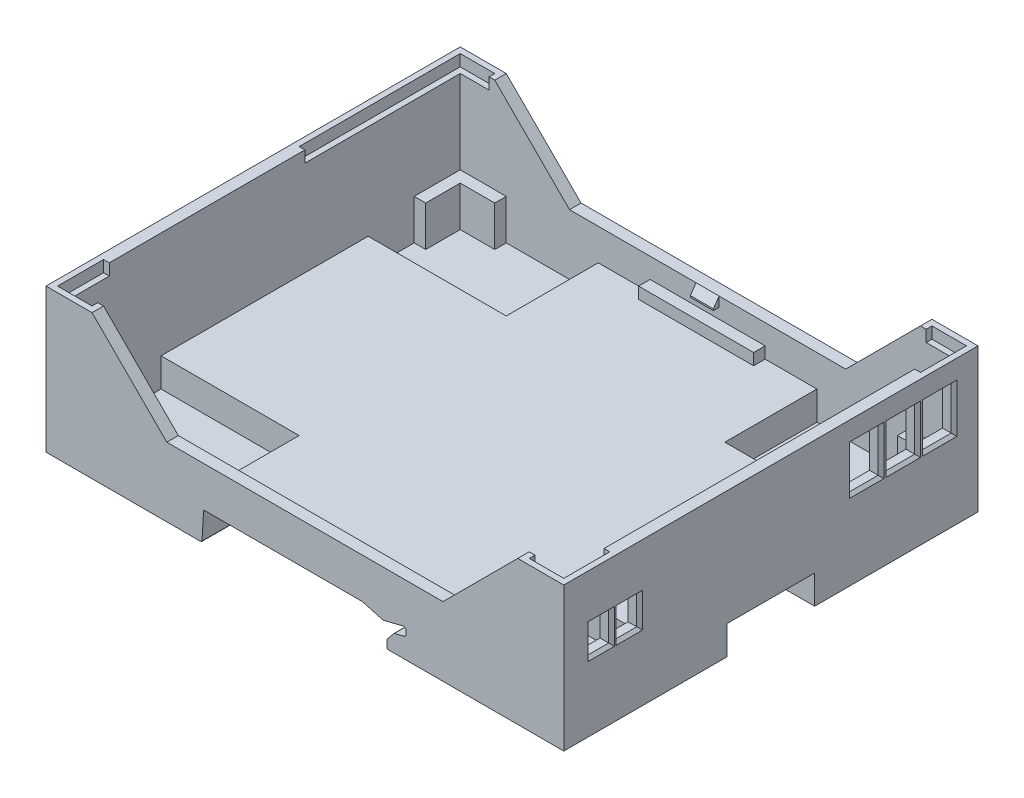
SolidWorks part; units mm, degrees
ref_plane "前视基准面" through (0, 0, 0) normal (0, 0, 1) x (1, 0, 0)
ref_plane "上视基准面" through (0, 0, 0) normal (0, 1, 0) x (1, 0, 0)
ref_plane "右视基准面" through (0, 0, 0) normal (1, 0, 0) x (0, 0, -1)
other "Configuration Table"
sketch "草图1" plane through (0, 0, 0) normal (0, 1, 0) x (1, 0, 0)
  line L1 (-45, -36) -> (45, -36)
  line L2 (-45, -36) -> (-45, 36)
  line L3 (-45, 36) -> (45, 36)
  line L4 (45, -36) -> (45, 36)
  dimension "D1" = 72
  dimension "D2" = 90
  dimension "D3" = 45
  dimension "D4" = 36
extrude "凸台-拉伸1" add sketch "草图1" along normal blind 25
sketch "草图4" plane through (0, 0, 36) normal (0, 0, 1) x (1, 0, 0)
  line L0 (14.3, 0) -> (14.3, 1.5)
  line L1 (-45, 0) -> (45, 0) construction
  line L2 (15.49, 2.9653) -> (17.6, 3.5)
  line L3 (17.6, 3.5) -> (17.6, 5)
  line L4 (17.6, 5) -> (13.5989, 4.0036)
  line L5 (13.5989, 4.0036) -> (10, 5)
  line L6 (10, 5) -> (-17.6, 5)
  line L7 (-17.6, 5) -> (-17.9, 0)
  line L8 (-17.9, 0) -> (14.3, 0)
  line L10 (14.3, 1.5) -> (15.49, 2.9653)
  dimension "D1" = 35.2
  dimension "D2" = 209.46
  dimension "D3" = 7.6
  dimension "D4" = 17.6
  dimension "D5" = 0.3
  dimension "D6" = 14.22
  dimension "D7" = 3.3
  dimension "D8" = 309.08
  dimension "D9" = 1.5
  dimension "D10" = 1.5
  dimension "D11" = 5
extrude "切除-拉伸1" cut sketch "草图4" against normal blind 72
fillet "圆角1" radius 0.5 2 edges at (17.6, 3.5, 0) (17.6, 5, 0)
fillet "圆角2" radius 0.2 5 edges at (-17.9, 0, 0) (-17.6, 5, 0) (15.49, 2.9653, 0) (14.3, 1.5, 0) (14.3, 0, 0)
sketch "草图5" plane through (-45, 0, 0) normal (-1, 0, 0) x (0, 0, 1)
  line L0 (5.6, 0) -> (5.6, 2.4)
  line L1 (-36, 0) -> (36, 0) construction
  line L2 (5.6, 2.4) -> (7.6, 2.4)
  line L3 (7.6, 2.4) -> (7.6, 5)
  line L4 (7.6, 5) -> (-7.6, 5)
  line L5 (-7.6, 5) -> (-7.6, 2.4)
  line L6 (-7.6, 2.4) -> (-5.6, 2.4)
  line L7 (-5.6, 2.4) -> (-5.6, 0)
  line L8 (-5.6, 0) -> (5.6, 0)
  dimension "D1" = 11.2
  dimension "D2" = 5.6
  dimension "D3" = 5
  dimension "D4" = 2.4
  dimension "D5" = 2.4
  dimension "D6" = 15.2
  dimension "D7" = 7.6
extrude "切除-拉伸2" cut sketch "草图5" against normal blind 28
ref_plane "基准面1" through (0, 0, 0) normal (0, 0, -1) x (-1, 0, 0)
fillet "圆角3" radius 0.5 2 edges at (-31.2058, 5, -7.6) (-31.2058, 5, 7.6)
sketch "草图9" plane through (45, 0, 0) normal (1, 0, 0) x (0, 0, -1)
  line L0 (-36, 0) -> (36, 0) construction
  line L1 (7.6, 0) -> (-7.6, 0)
  line L2 (7.6, 0) -> (7.6, 5)
  line L3 (7.6, 5) -> (-7.6, 5)
  line L4 (-7.6, 0) -> (-7.6, 5)
  dimension "D1" = 15.2
  dimension "D2" = 7.6
  dimension "D3" = 5
extrude "切除-拉伸4" cut sketch "草图9" against normal blind 36
sketch "草图10" plane through (0, 0, 7.6) normal (0, 0, -1) x (-1, 0, 0)
  line L0 (-14.5, 0) -> (-45, 0) construction
  line L1 (-10, 5) -> (-17.6, 5)
  line L2 (-10, 5) -> (-10, 0)
  line L3 (-10, 0) -> (-17.6, 0)
  line L4 (-17.6, 5) -> (-17.6, 0)
  line L5 (-17.6, 4.3602) -> (-17.6, 3.8891) construction
extrude "切除-拉伸5" cut sketch "草图10" against normal blind 4
mirror "镜向2" about plane through (0, 0, 0) normal (0, 0, -1) of "切除-拉伸5"
sketch "草图11" plane through (0, 0, 36) normal (0, 0, 1) x (1, 0, 0)
  line L0 (-37, 25) -> (37, 25)
  line L1 (-45, 25) -> (45, 25) construction
  line L2 (37, 25) -> (24, 12)
  line L3 (24, 12) -> (-24, 12)
  line L4 (-24, 12) -> (-37, 25)
  line L5 (-45, 25) -> (-45, 0) construction
  line L6 (45, 25) -> (45, 0) construction
  dimension "D1" = 8
  dimension "D2" = 8
  dimension "D3" = 13
  dimension "D4" = 135
  dimension "D5" = 135
extrude "切除-拉伸6" cut sketch "草图11" against normal blind 72
sketch "草图12" plane through (0, 25, 0) normal (0, 1, 0) x (1, 0, 0)
  line L0 (-37, 36) -> (-45, 36) construction
  line L1 (-43, 34) -> (43, 34)
  line L2 (-43, 34) -> (-43, -34)
  line L3 (-43, -34) -> (43, -34)
  line L4 (43, 34) -> (43, -34)
  line L5 (45, -36) -> (45, 36) construction
  line L6 (37, -36) -> (45, -36) construction
  line L7 (-45, 36) -> (-45, -36) construction
  dimension "D1" = 2
  dimension "D2" = 2
  dimension "D3" = 2
  dimension "D4" = 2
extrude "切除-拉伸7" cut sketch "草图12" against normal blind 18.5
sketch "草图13" plane through (0, 6.5, 0) normal (0, 1, 0) x (1, 0, 0)
  line L1 (43, -34) -> (19, -34)
  line L2 (43, -34) -> (43, -18)
  line L3 (43, -18) -> (19, -18)
  line L4 (19, -34) -> (19, -18)
  dimension "D1" = 16
  dimension "D2" = 24
extrude "切除-拉伸8" cut sketch "草图13" against normal blind 5
ref_plane "基准面3" through (0, 0, 0) normal (-1, 0, 0) x (0, 0, 1)
mirror "镜向3" about plane through (0, 0, 0) normal (0, 0, -1) of "切除-拉伸8"
mirror "镜向4" about plane through (0, 0, 0) normal (-1, 0, 0) of "镜向3"
sketch "草图14" plane through (0, 1.5, 0) normal (0, 1, 0) x (1, 0, 0)
  line L0 (35, -34) -> (43, -34)
  line L1 (37, -34) -> (43, -34) construction
  line L2 (43, -34) -> (43, -26)
  line L3 (43, -34) -> (43, -18) construction
  line L4 (43, -26) -> (41, -26)
  line L5 (41, -26) -> (41, -32)
  line L6 (41, -32) -> (35, -32)
  line L7 (35, -32) -> (35, -34)
  dimension "D1" = 2
  dimension "D2" = 2
  dimension "D3" = 8
  dimension "D4" = 8
extrude "凸台-拉伸4" add sketch "草图14" along normal blind 7
mirror "镜向5" about plane through (0, 0, 0) normal (0, 0, -1) of "凸台-拉伸4"
mirror "镜向6" about plane through (0, 0, 0) normal (-1, 0, 0) of "镜向5"
sketch "草图15" plane through (0, 6.5, 0) normal (0, 1, 0) x (1, 0, 0)
  line L12 (19, 34) -> (-19, 34) construction
  line L13 (-10, 34) -> (10, 34)
  line L14 (-10, 34) -> (-10, 32)
  line L15 (-10, 32) -> (10, 32)
  line L16 (10, 34) -> (10, 32)
  line L18 (0, 13.75) -> (0, -13.75) construction
  dimension "D1" = 20
  dimension "D2" = 10
  dimension "D3" = 2
extrude "凸台-拉伸5" add sketch "草图15" along normal blind 2
mirror "镜向7" about plane through (0, 0, 0) normal (0, 0, -1) of "凸台-拉伸5"
sketch "草图17" plane through (0, 0, -34) normal (0, 0, 1) x (1, 0, 0)
  line L0 (-24, 12) -> (24, 12) construction
  line L1 (-2, 12) -> (2, 12)
  line L2 (-2, 12) -> (-2, 10.3)
  line L3 (-2, 10.3) -> (2, 10.3)
  line L4 (2, 12) -> (2, 10.3)
  line L5 (10, 8.5) -> (-10, 8.5) construction
  line L6 (0, 13.75) -> (0, -13.75) construction
  dimension "D1" = 1.8
  dimension "D2" = 4
  dimension "D3" = 2
extrude "凸台-拉伸6" add sketch "草图17" along normal blind 1
chamfer "倒角3" distance 1 angle 55 1 edges at (0, 12, -33) first distance on face at (0, 12, -34.25)
mirror "镜向8" about plane through (0, 0, 0) normal (0, 0, -1) of "倒角3", "凸台-拉伸6"
sketch "草图20" plane through (0, 8.5, 0) normal (0, 1, 0) x (1, 0, 0)
  line L0 (-10, -33.8) -> (10, -33.8)
  line L1 (19, -33.8) -> (42.8, -33.8)
  line L14 (-24, 34) -> (-2, 34) construction
  line L16 (-42.8, 33.8) -> (-19, 33.8)
  line L17 (-42.8, 33.8) -> (-42.8, -33.8)
  line L20 (-42.8, -33.8) -> (-19, -33.8)
  line L21 (42.8, 33.8) -> (42.8, -33.8)
  line L25 (-43, 34) -> (-43, -34) construction
  line L26 (43, -18) -> (43, 18) construction
  line L63 (35, -34) -> (43, -34) construction
  line L64 (-19, 33.8) -> (-19, 28.8)
  line L65 (-19, 18) -> (-19, 34) construction
  line L66 (-19, 18) -> (-19, 34) construction
  line L67 (-19, 28.8) -> (-10, 28.8)
  line L68 (-10, 28.8) -> (-10, 33.8)
  line L69 (-10, 34) -> (-10, 32) construction
  line L70 (19, 33.8) -> (19, 28.8)
  line L71 (19, 18) -> (19, 34) construction
  line L72 (19, 28.8) -> (10, 28.8)
  line L73 (10, 28.8) -> (10, 33.8)
  line L74 (10, 32) -> (10, 34) construction
  line L75 (-10, -33.8) -> (-10, -28.8)
  line L76 (-10, -28.8) -> (-19, -28.8)
  line L77 (-19, -18) -> (-19, -34) construction
  line L78 (-19, -28.8) -> (-19, -33.8)
  line L79 (-19, -18) -> (-19, -34) construction
  line L80 (19, -33.8) -> (19, -28.8)
  line L81 (19, -18) -> (19, -34) construction
  line L82 (19, -28.8) -> (10, -28.8)
  line L83 (10, -28.8) -> (10, -33.8)
  line L84 (10, -32) -> (10, -34) construction
  line L85 (19, 33.8) -> (42.8, 33.8)
  line L86 (-10, 33.8) -> (10, 33.8)
  dimension "D1" = 0.2
  dimension "D2" = 0.2
  dimension "D3" = 0.2
  dimension "D4" = 0.2
  dimension "D5" = 5
  dimension "D6" = 5
  dimension "D7" = 5
  dimension "D8" = 5
sketch "草图22" plane through (0, 0, 0) normal (0, -1, 0) x (1, 0, 0)
  line L0 (-17.756, 7.6) -> (-17.63, 7.6) construction
  line L1 (-17.756, 5.6) -> (-21.756, 5.6)
  line L2 (-17.756, 5.6) -> (-17.756, 7.6)
  line L3 (-17.756, 7.6) -> (-21.756, 7.6)
  line L4 (-21.756, 5.6) -> (-21.756, 7.6)
  line L5 (-18.0884, 5.6) -> (-45, 5.6) construction
  line L6 (-17.756, 5.6) -> (-17.756, 7.6) construction
  dimension "D1" = 4
extrude "切除-拉伸9" cut sketch "草图22" against normal blind 2.6
ref_plane "基准面4" through (0, 0, 0) normal (0, 0, 1) x (1, 0, 0)
mirror "镜向9" about plane through (0, 0, 0) normal (0, 0, 1) of "切除-拉伸9"
sketch "草图23" plane through (0, 5, 0) normal (0, 1, 0) x (1, 0, 0)
  line L3 (-31.2, 7.6) -> (-28.2, 7.6)
  line L4 (-28, 7.6) -> (-27, 8.6)
  line L7 (-28, 7.6) -> (-25, 7.6)
  line L8 (-21.756, 7.6) -> (-45, 7.6) construction
  line L9 (-27, 8.6) -> (-26, 8.6)
  line L10 (-26, 8.6) -> (-25, 7.6)
  line L11 (-31.2, 7.6) -> (-30.2, 8.6)
  line L12 (-30.2, 8.6) -> (-29.2, 8.6)
  line L13 (-29.2, 8.6) -> (-28.2, 7.6)
  line L14 (-45, 36) -> (-45, -36) construction
  dimension "D1" = 0.2
  dimension "D4" = 45
  dimension "D5" = 3
  dimension "D6" = 45
  dimension "D7" = 3
  dimension "D8" = 1
  dimension "D9" = 1
  dimension "D10" = 13.8
extrude "切除-拉伸15" cut sketch "草图23" against normal blind 2.4
ref_plane "基准面5" through (0, 0, 3) normal (0, 0, 1) x (1, 0, 0)
sketch "草图24" plane through (0, 0, 3) normal (0, 0, 1) x (1, 0, 0)
  line L0 (-45, 5) -> (-45, 7.5981)
  line L1 (-45, 7.5981) -> (-43.5, 5)
  line L2 (-43.5, 5) -> (-45, 5)
  line L3 (10, 5) -> (17.6, 5) construction
  line L4 (-45, 25) -> (-45, 0) construction
  dimension "D1" = 1.5
  dimension "D2" = 60
extrude "切除-拉伸17" cut sketch "草图24" against normal blind 6
sketch "草图25" plane through (0, 25, 0) normal (0, 1, 0) x (1, 0, 0)
  line L28 (43, 34) -> (37, 34) construction
  line L29 (43, -34) -> (43, 34) construction
  line L35 (43, 27) -> (41, 27)
  line L36 (44, 27) -> (43, 27)
  line L37 (44, 35) -> (44, 27)
  line L38 (38, 35) -> (44, 35)
  line L40 (38, 34) -> (43, 34)
  line L41 (38, 36) -> (38, 34)
  line L42 (38, 35) -> (38, 34)
  line L43 (43, 34) -> (43, 27)
  line L44 (43, 34) -> (43, 26) construction
  dimension "D1" = 1
  dimension "D2" = 1
  dimension "D3" = 1
  dimension "D4" = 1
extrude "切除-拉伸18" cut sketch "草图25" against normal blind 2
mirror "镜向10" about plane through (0, 0, 0) normal (0, 0, 1) of "切除-拉伸18"
mirror "镜向11" about plane through (0, 0, 0) normal (-1, 0, 0) of "镜向10"
sketch "草图26" plane through (45, 0, 0) normal (1, 0, 0) x (0, 0, -1)
  line L0 (36, 25) -> (36, 0) construction
  line L1 (26.84, 21.2) -> (31.84, 21.2)
  line L2 (26.84, 21.2) -> (26.84, 13.7)
  line L3 (26.84, 13.7) -> (31.84, 13.7)
  line L4 (31.84, 21.2) -> (31.84, 13.7)
  line L5 (20.49, 21.2) -> (25.49, 21.2)
  line L6 (20.49, 21.2) -> (20.49, 13.7)
  line L7 (20.49, 13.7) -> (25.49, 13.7)
  line L8 (25.49, 21.2) -> (25.49, 13.7)
  line L9 (14.14, 21.2) -> (19.14, 21.2)
  line L10 (14.14, 21.2) -> (14.14, 13.7)
  line L11 (14.14, 13.7) -> (19.14, 13.7)
  line L12 (19.14, 21.2) -> (19.14, 13.7)
  line L13 (7.6, 0) -> (36, 0) construction
  line L14 (-36, 0) -> (-7.6, 0) construction
  line L15 (-31.3, 16.87) -> (-27.7, 16.87)
  line L16 (-31.3, 16.87) -> (-31.3, 11.87)
  line L17 (-31.3, 11.87) -> (-27.7, 11.87)
  line L18 (-27.7, 16.87) -> (-27.7, 11.87)
  line L19 (-26.42, 16.87) -> (-22.82, 16.87)
  line L20 (-26.42, 16.87) -> (-26.42, 11.87)
  line L21 (-26.42, 11.87) -> (-22.82, 11.87)
  line L22 (-22.82, 16.87) -> (-22.82, 11.87)
  line L23 (-36, 25) -> (-36, 0) construction
  dimension "D1" = 1.35
  dimension "D2" = 1.35
  dimension "D3" = 5
  dimension "D4" = 5
  dimension "D5" = 5
  dimension "D6" = 4.16
  dimension "D7" = 13.7
  dimension "D8" = 7.5
  dimension "D9" = 5
  dimension "D10" = 3.6
  dimension "D11" = 3.6
  dimension "D12" = 1.28
  dimension "D13" = 11.87
  dimension "D14" = 4.7
extrude "切除-拉伸19" cut sketch "草图26" against normal blind 2.5
chamfer "倒角4" distance 0.5 angle 45 20 edges at (45, 17.45, -26.84) (45, 13.7, -29.34) (45, 17.45, -31.84) (45, 21.2, -29.34) (45, 21.2, -22.99) (45, 17.45, -20.49) (45, 13.7, -22.99) (45, 17.45, -25.49) (45, 21.2, -16.64) (45, 17.45, -19.14) (45, 13.7, -16.64) (45, 17.45, -14.14) (45, 14.37, 31.3) (45, 11.87, 29.5) (45, 16.87, 29.5) (45, 14.37, 27.7) (45, 14.37, 26.42) (45, 11.87, 24.62) (45, 16.87, 24.62) (45, 14.37, 22.82)
mirror "镜向12" about plane through (0, 0, 0) normal (0, 0, -1) of "切除-拉伸15"
sketch "草图27" plane through (0, 25, 0) normal (0, 1, 0) x (1, 0, 0)
  line L0 (-43, 27) -> (-43, -27) construction
  line L1 (-44, 27) -> (-43, 27)
  line L2 (-44, 27) -> (-44, 7)
  line L3 (-44, 7) -> (-43, 7)
  line L4 (-43, 27) -> (-43, 7)
  dimension "D1" = 20
extrude "切除-拉伸20" cut sketch "草图27" against normal blind 2
